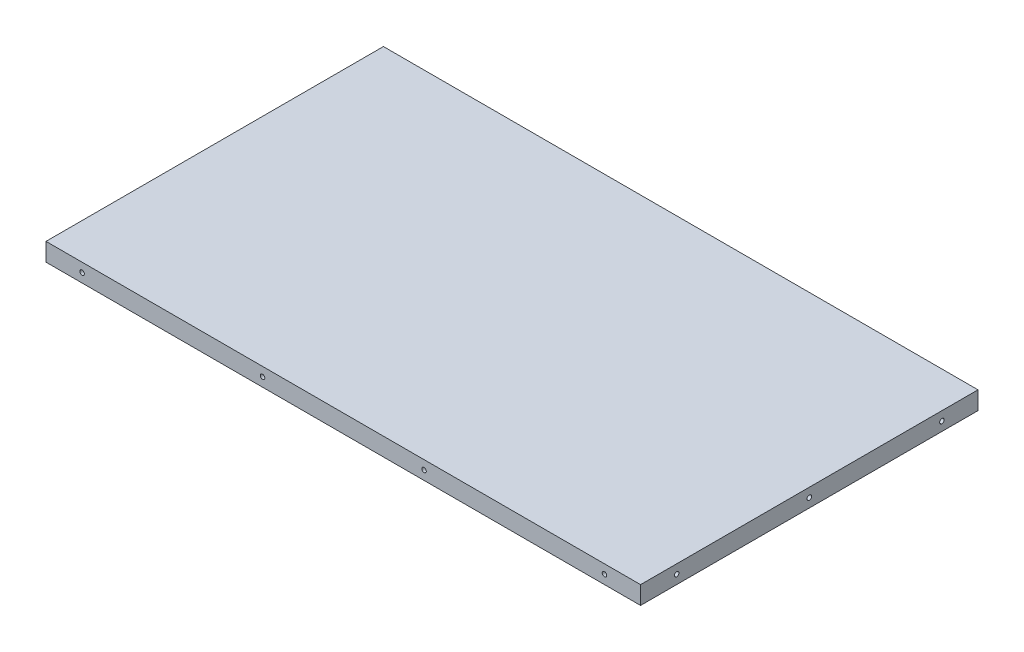
SolidWorks part; units mm, degrees
ref_plane "Front Plane" through (0, 0, 0) normal (0, 0, 1) x (1, 0, 0)
ref_plane "Top Plane" through (0, 0, 0) normal (0, 1, 0) x (1, 0, 0)
ref_plane "Right Plane" through (0, 0, 0) normal (1, 0, 0) x (0, 0, -1)
sketch "Sketch1" plane through (0, 0, 0) normal (0, 1, 0) x (1, 0, 0)
  line L1 (0, 0) -> (329.5, 0)
  line L2 (0, 0) -> (0, 187)
  line L3 (0, 187) -> (329.5, 187)
  line L4 (329.5, 0) -> (329.5, 187)
  dimension "D1" = 187
  dimension "D2" = 329.5
extrude "Boss-Extrude1" add sketch "Sketch1" along normal blind 10
sketch "Sketch2" plane through (0, 0, 0) normal (0, 0, 1) x (1, 0, 0)
  line L0 (0, 5) -> (329.5, 5) construction
  line L1 (0, 10) -> (0, 0) construction
  line L2 (329.5, 10) -> (329.5, 0) construction
  circle A0 centre (20, 5) radius 1.25
  circle A1 centre (120, 5) radius 1.25
  circle A2 centre (209.5, 5) radius 1.25
  circle A3 centre (309.5, 5) radius 1.25
  dimension "D1" = 2.5
  dimension "D2" = 20
  dimension "D3" = 100
  dimension "D4" = 20
  dimension "D5" = 100
extrude "Cut-Extrude1" cut sketch "Sketch2" against normal blind 10
extrude "Cut-Extrude2" cut sketch "Sketch2<2>" along normal blind 10 from surface starting at face at (164.75, 5, -187)
sketch "Sketch2<2>" plane through (0, 0, 0) normal (0, 0, 1) x (1, 0, 0) same geometry as "Sketch2"
sketch "Sketch3" plane through (0, 0, 0) normal (-1, 0, 0) x (0, 0, 1)
  line L0 (-187, 5) -> (0, 5) construction
  line L1 (-187, 10) -> (-187, 0) construction
  line L2 (0, 10) -> (0, 0) construction
  circle A0 centre (-167, 5) radius 1.25
  circle A1 centre (-93.5, 5) radius 1.25
  circle A2 centre (-20, 5) radius 1.25
  point P12 (-93.5, 5)
  dimension "D1" = 2.5
  dimension "D2" = 20
  dimension "D3" = 20
extrude "Cut-Extrude3" cut sketch "Sketch3" against normal blind 10
extrude "Cut-Extrude4" cut sketch "Sketch3<2>" along normal blind 10 from surface starting at face at (329.5, 5, -93.5)
sketch "Sketch3<2>" plane through (0, 0, 0) normal (-1, 0, 0) x (0, 0, 1) same geometry as "Sketch3"
